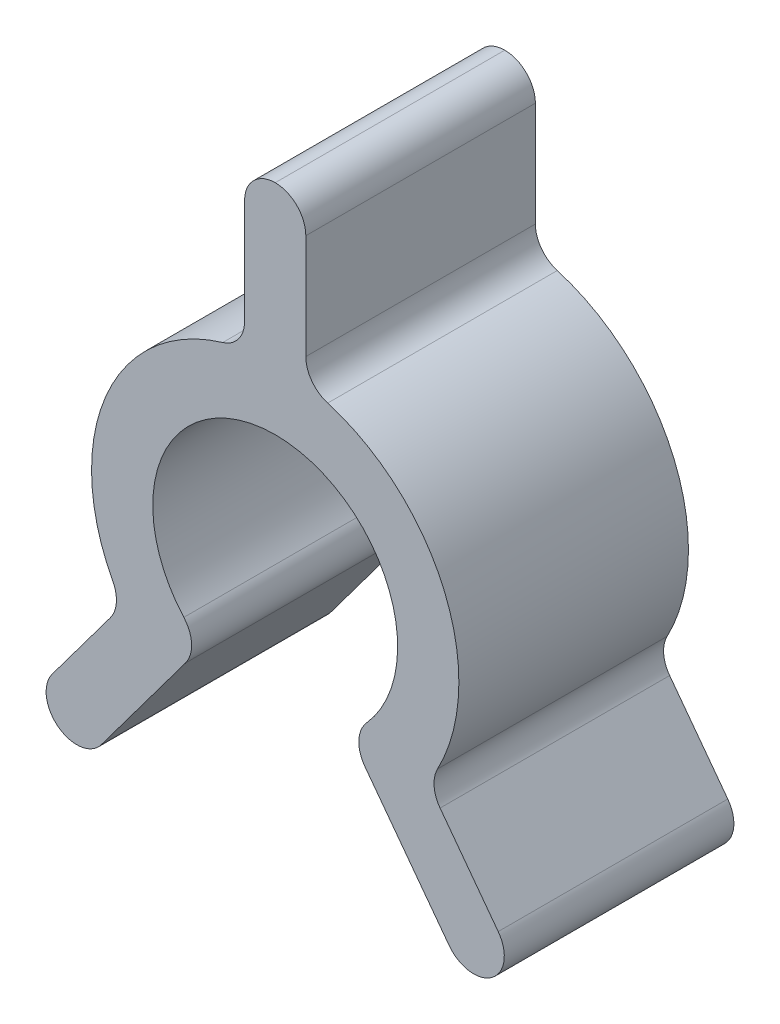
SolidWorks part; units mm, degrees
ref_plane "Front Plane" through (0, 0, 0) normal (0, 0, 1) x (1, 0, 0)
ref_plane "Top Plane" through (0, 0, 0) normal (0, 1, 0) x (1, 0, 0)
ref_plane "Right Plane" through (0, 0, 0) normal (1, 0, 0) x (0, 0, -1)
sketch "Sketch1" plane through (0, 0, 0) normal (0, 0, 1) x (1, 0, 0)
  line L0 (2.3926, -3.2055) -> (3.5889, -4.8083)
  line L1 (3.5889, -4.8083) -> (6.2806, -8.4145)
  line L2 (6.2806, -8.4145) -> (7.8833, -7.2182)
  line L3 (7.8833, -7.2182) -> (4.9864, -3.337)
  line L4 (-3.5889, -4.8083) -> (-6.2806, -8.4145)
  line L5 (-6.2806, -8.4145) -> (-7.8833, -7.2182)
  line L6 (-7.8833, -7.2182) -> (-4.9864, -3.337)
  line L7 (-3.5889, -4.8083) -> (-2.3926, -3.2055)
  line L8 (0, 4) -> (0, 11.1276) construction
  line L9 (1, 4) -> (1, 11.1276)
  line L10 (-1, 4) -> (-1, 11.1276)
  line L11 (1, 4) -> (-1, 4)
  line L12 (1, 11.1276) -> (-1, 11.1276)
  line L13 (0, 4) -> (0, 11.1276) construction
  circle A0 centre (0, 0) radius 4
  circle A1 centre (0, 0) radius 6
  dimension "D1" = 2
  dimension "D4" = 8
  dimension "D2" = 2
  dimension "D3" = 2
  dimension "D5" = 4.5
  dimension "D6" = 1
  dimension "D7" = 1
extrude "Boss-Extrude1" add sketch "Sketch1" along normal blind 7.5 contours A1 L6 L5 L4 | A1 L7 A0 L0 | A1 L1 L2 L3 | L9 A1 L10 L11 | A1 L9 L12 L10 | L0 A1 L9 L11 A0 region at (3.9203, 0.8889, 0) region at (5.7115, -5.9597, 0) region at (-3.9203, 0.8889, 0) region at (-5.7115, -5.9597, 0) region at (0, 4.9862, 0) region at (0, 8.5498, 0)
fillet "Fillet1" radius 1 12 edges at (6.2806, -8.4145, 3.75) (7.8833, -7.2182, 3.75) (-6.2806, -8.4145, 3.75) (-7.8833, -7.2182, 3.75) (-4.9864, -3.337, 3.75) (2.3926, -3.2055, 3.75) (-2.3926, -3.2055, 3.75) (4.9864, -3.337, 3.75) (-1, 5.9161, 3.75) (-1, 11.1276, 3.75) (1, 11.1276, 3.75) (1, 5.9161, 3.75)
sketch "Sketch2" plane through (0, 0, 0) normal (0, 0, -1) x (-1, 0, 0)
  line L0 (-3.4641, 2) -> (3.4641, 2)
  line L1 (0, 4) -> (0, 2) construction
  line L2 (-0.2, 4) -> (-0.2, 2)
  line L3 (0.2, 4) -> (0.2, 2)
  arc A0 (2.9854, -2.6623) -> (-2.9854, -2.6623) centre (0, 0) ccw construction
  arc A1 (3.4641, 2) -> (-3.4641, 2) centre (0, 0) ccw
  arc A2 (-0.2, 4) -> (0.2, 4) centre (0, 4) cw
  arc A3 (-0.2, 2) -> (0.2, 2) centre (0, 2) ccw
  point P5 (0, 4)
  arc M13 (-2.9854, -2.6623) -> (2.9854, -2.6623) centre (0, 0) cw
  dimension "D1" = 2
  dimension "D2" = 0.2
  dimension "D3" = 0.2
extrude "Boss-Extrude2" add sketch "Sketch2" against normal blind 2 contours L2 L0 M13 | L3 L0 M13 region at (1.4681, 2.8042, 0) region at (-1.4681, 2.8042, 0)
fillet "Fillet2" radius 0.2 4 edges at (0.2, 3.995, 1) (-0.2, 3.995, 1) (-0.2, 2, 1) (0.2, 2, 1)
